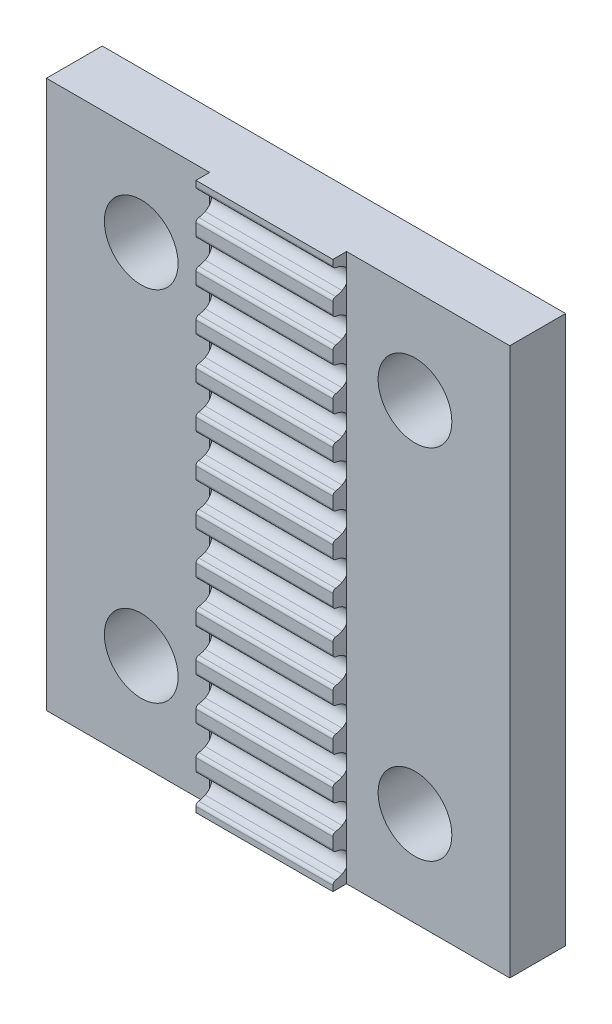
SolidWorks part; units mm, degrees
ref_plane "Piano frontale" through (0, 0, 0) normal (0, 0, 1) x (1, 0, 0)
ref_plane "Piano superiore" through (0, 0, 0) normal (0, 1, 0) x (1, 0, 0)
ref_plane "Piano destro" through (0, 0, 0) normal (1, 0, 0) x (0, 0, -1)
sketch "Schizzo1" plane through (0, 0, 0) normal (0, 0, 1) x (1, 0, 0)
  line L1 (-11, -13) -> (11, -13)
  line L2 (-11, -13) -> (-11, 13)
  line L3 (-11, 13) -> (11, 13)
  line L4 (11, -13) -> (11, 13)
  line L5 (-11, -13) -> (11, 13) construction
  line L6 (-11, 13) -> (11, -13) construction
  line L7 (-6.5, 8.5) -> (6.5, 8.5) construction
  line L8 (-6.5, 8.5) -> (-6.5, -8.5) construction
  line L9 (-6.5, -8.5) -> (6.5, -8.5) construction
  line L10 (6.5, 8.5) -> (6.5, -8.5) construction
  line L11 (-6.5, 8.5) -> (6.5, -8.5) construction
  line L12 (-6.5, -8.5) -> (6.5, 8.5) construction
  line L13 (-3.25, 13) -> (3.25, 13)
  line L14 (-3.25, 13) -> (-3.25, -13)
  line L15 (-3.25, -13) -> (3.25, -13)
  line L16 (3.25, 13) -> (3.25, -13)
  line L17 (-3.25, 13) -> (3.25, -13) construction
  line L18 (-3.25, -13) -> (3.25, 13) construction
  circle A0 centre (-6.5, 8.5) radius 1.75
  circle A1 centre (6.5, 8.5) radius 1.75
  circle A2 centre (6.5, -8.5) radius 1.75
  circle A3 centre (-6.5, -8.5) radius 1.75
  point P0 (0, 0)
  point P6 (0, 0)
  point P7 (0, 0)
  point P15 (0, 0)
  point P20 (0, 0)
  dimension "D3" = 3.5
  dimension "D1" = 22
  dimension "D2" = 26
  dimension "D5" = 6.5
  dimension "D6" = 4.5
  dimension "D7" = 4.5
extrude "Estrusione-Estrusione1" add sketch "Schizzo1" along normal blind 1 contours L14 L3 L2 L1 A3 A0 | L16 L3 L14 L1 | L3 L16 L1 L4 A2 A1 region at (-7.191, 0, 0) region at (0, 0, 0) region at (7.191, 0, 0)
extrude "Estrusione-Estrusione2" add sketch "Schizzo1<3>" along normal blind 1.65 contours L14 L15 L16 L13
sketch "Schizzo1<3>" plane through (0, 0, 0) normal (0, 0, 1) x (1, 0, 0) same geometry as "Schizzo1"
extrude "Estrusione-Estrusione3" add sketch "Schizzo1<5>" against normal blind 1.65 contours L14 L3 L2 L1 A3 A0 | L16 L3 L14 L1 | L3 L16 L1 L4 A2 A1 region at (-7.191, 0, 0) region at (0, 0, 0) region at (7.191, 0, 0)
sketch "Schizzo1<5>" plane through (0, 0, 0) normal (0, 0, 1) x (1, 0, 0) same geometry as "Schizzo1"
sketch "Schizzo2" plane through (-3.25, 0, 0) normal (-1, 0, 0) x (0, 0, 1)
  line L0 (1.65, 13) -> (1.65, 12.7402)
  line L2 (1.65, 13) -> (1, 13) construction
  line L3 (1.65, 13) -> (1, 13) construction
  line L4 (1.65, 11) -> (1.65, 10.7402)
  line L5 (2.28, 11) -> (2.28, 9)
  line L6 (1.65, 9) -> (1.65, 9.2598)
  line L7 (1.65, 13) -> (1.65, -13) construction
  line L8 (1.65, 13) -> (1.65, -13) construction
  line L9 (0.9, 12) -> (2.28, 12) construction
  line L10 (2.28, 13) -> (2.28, 11)
  line L11 (1.65, 11) -> (1.65, 11.2598)
  line L12 (1.65, 11) -> (1, 11) construction
  line L13 (0.9, 10) -> (2.28, 10) construction
  line L14 (1.65, 9) -> (1.65, 8.7402)
  line L15 (2.28, 9) -> (2.28, 7)
  line L16 (1.65, 7) -> (1.65, 7.2598)
  line L17 (1.65, 9) -> (1, 9) construction
  line L18 (0.9, 8) -> (2.28, 8) construction
  line L19 (1.65, 7) -> (1.65, 6.7402)
  line L20 (2.28, 7) -> (2.28, 5)
  line L21 (1.65, 5) -> (1.65, 5.2598)
  line L22 (1.65, 7) -> (1, 7) construction
  line L23 (0.9, 6) -> (2.28, 6) construction
  line L24 (1.65, 5) -> (1.65, 4.7402)
  line L25 (2.28, 5) -> (2.28, 3)
  line L26 (1.65, 3) -> (1.65, 3.2598)
  line L27 (1.65, 5) -> (1, 5) construction
  line L28 (0.9, 4) -> (2.28, 4) construction
  line L29 (1.65, 3) -> (1.65, 2.7402)
  line L30 (2.28, 3) -> (2.28, 1)
  line L31 (1.65, 1) -> (1.65, 1.2598)
  line L32 (1.65, 3) -> (1, 3) construction
  line L33 (0.9, 2) -> (2.28, 2) construction
  line L34 (1.65, 1) -> (1.65, 0.7402)
  line L35 (2.28, 1) -> (2.28, -1)
  line L36 (1.65, -1) -> (1.65, -0.7402)
  line L37 (1.65, 1) -> (1, 1) construction
  line L38 (0.9, 0) -> (2.28, 0) construction
  line L39 (1.65, -1) -> (1.65, -1.2598)
  line L40 (2.28, -1) -> (2.28, -3)
  line L41 (1.65, -3) -> (1.65, -2.7402)
  line L42 (1.65, -1) -> (1, -1) construction
  line L43 (0.9, -2) -> (2.28, -2) construction
  line L44 (1.65, -3) -> (1.65, -3.2598)
  line L45 (2.28, -3) -> (2.28, -5)
  line L46 (1.65, -5) -> (1.65, -4.7402)
  line L47 (1.65, -3) -> (1, -3) construction
  line L48 (0.9, -4) -> (2.28, -4) construction
  line L49 (1.65, -5) -> (1.65, -5.2598)
  line L50 (2.28, -5) -> (2.28, -7)
  line L51 (1.65, -7) -> (1.65, -6.7402)
  line L52 (1.65, -5) -> (1, -5) construction
  line L53 (0.9, -6) -> (2.28, -6) construction
  line L54 (1.65, -7) -> (1.65, -7.2598)
  line L55 (2.28, -7) -> (2.28, -9)
  line L56 (1.65, -9) -> (1.65, -8.7402)
  line L57 (1.65, -7) -> (1, -7) construction
  line L58 (0.9, -8) -> (2.28, -8) construction
  line L59 (1.65, -9) -> (1.65, -9.2598)
  line L60 (2.28, -9) -> (2.28, -11)
  line L61 (1.65, -11) -> (1.65, -10.7402)
  line L62 (1.65, -9) -> (1, -9) construction
  line L63 (0.9, -10) -> (2.28, -10) construction
  line L64 (1.65, -11) -> (1.65, -11.2598)
  line L65 (2.28, -11) -> (2.28, -13)
  line L66 (1.65, -13) -> (1.65, -12.7402)
  line L67 (1.65, -11) -> (1, -11) construction
  line L68 (0.9, -12) -> (2.28, -12) construction
  line L69 (1.65, -13) -> (2.28, -13)
  line L70 (2.28, 13) -> (1.65, 13)
  arc A0 (1.65, 12.7402) -> (1.5196, 12.5915) centre (1.5, 12.7402) cw
  arc A1 (1.2118, 12.4989) -> (1.5196, 12.5915) centre (1.65, 11.6) cw
  arc A2 (1.65, 10.7402) -> (1.5196, 10.5915) centre (1.5, 10.7402) cw
  arc A3 (1.2118, 10.4989) -> (1.5196, 10.5915) centre (1.65, 9.6) cw
  arc A4 (1.2118, 10.4989) -> (1.2118, 9.5011) centre (1.455, 10) ccw
  arc A5 (1.2118, 12.4989) -> (1.2118, 11.5011) centre (1.455, 12) ccw
  arc A6 (1.2118, 11.5011) -> (1.5196, 11.4085) centre (1.65, 12.4) ccw
  arc A7 (1.65, 11.2598) -> (1.5196, 11.4085) centre (1.5, 11.2598) ccw
  arc A8 (1.2118, 9.5011) -> (1.5196, 9.4085) centre (1.65, 10.4) ccw
  arc A9 (1.65, 9.2598) -> (1.5196, 9.4085) centre (1.5, 9.2598) ccw
  arc A10 (1.65, 8.7402) -> (1.5196, 8.5915) centre (1.5, 8.7402) cw
  arc A11 (1.2118, 8.4989) -> (1.5196, 8.5915) centre (1.65, 7.6) cw
  arc A12 (1.2118, 8.4989) -> (1.2118, 7.5011) centre (1.455, 8) ccw
  arc A13 (1.2118, 7.5011) -> (1.5196, 7.4085) centre (1.65, 8.4) ccw
  arc A14 (1.65, 7.2598) -> (1.5196, 7.4085) centre (1.5, 7.2598) ccw
  arc A15 (1.65, 6.7402) -> (1.5196, 6.5915) centre (1.5, 6.7402) cw
  arc A16 (1.2118, 6.4989) -> (1.5196, 6.5915) centre (1.65, 5.6) cw
  arc A17 (1.2118, 6.4989) -> (1.2118, 5.5011) centre (1.455, 6) ccw
  arc A18 (1.2118, 5.5011) -> (1.5196, 5.4085) centre (1.65, 6.4) ccw
  arc A19 (1.65, 5.2598) -> (1.5196, 5.4085) centre (1.5, 5.2598) ccw
  arc A20 (1.65, 4.7402) -> (1.5196, 4.5915) centre (1.5, 4.7402) cw
  arc A21 (1.2118, 4.4989) -> (1.5196, 4.5915) centre (1.65, 3.6) cw
  arc A22 (1.2118, 4.4989) -> (1.2118, 3.5011) centre (1.455, 4) ccw
  arc A23 (1.2118, 3.5011) -> (1.5196, 3.4085) centre (1.65, 4.4) ccw
  arc A24 (1.65, 3.2598) -> (1.5196, 3.4085) centre (1.5, 3.2598) ccw
  arc A25 (1.65, 2.7402) -> (1.5196, 2.5915) centre (1.5, 2.7402) cw
  arc A26 (1.2118, 2.4989) -> (1.5196, 2.5915) centre (1.65, 1.6) cw
  arc A27 (1.2118, 2.4989) -> (1.2118, 1.5011) centre (1.455, 2) ccw
  arc A28 (1.2118, 1.5011) -> (1.5196, 1.4085) centre (1.65, 2.4) ccw
  arc A29 (1.65, 1.2598) -> (1.5196, 1.4085) centre (1.5, 1.2598) ccw
  arc A30 (1.65, 0.7402) -> (1.5196, 0.5915) centre (1.5, 0.7402) cw
  arc A31 (1.2118, 0.4989) -> (1.5196, 0.5915) centre (1.65, -0.4) cw
  arc A32 (1.2118, 0.4989) -> (1.2118, -0.4989) centre (1.455, 0) ccw
  arc A33 (1.2118, -0.4989) -> (1.5196, -0.5915) centre (1.65, 0.4) ccw
  arc A34 (1.65, -0.7402) -> (1.5196, -0.5915) centre (1.5, -0.7402) ccw
  arc A35 (1.65, -1.2598) -> (1.5196, -1.4085) centre (1.5, -1.2598) cw
  arc A36 (1.2118, -1.5011) -> (1.5196, -1.4085) centre (1.65, -2.4) cw
  arc A37 (1.2118, -1.5011) -> (1.2118, -2.4989) centre (1.455, -2) ccw
  arc A38 (1.2118, -2.4989) -> (1.5196, -2.5915) centre (1.65, -1.6) ccw
  arc A39 (1.65, -2.7402) -> (1.5196, -2.5915) centre (1.5, -2.7402) ccw
  arc A40 (1.65, -3.2598) -> (1.5196, -3.4085) centre (1.5, -3.2598) cw
  arc A41 (1.2118, -3.5011) -> (1.5196, -3.4085) centre (1.65, -4.4) cw
  arc A42 (1.2118, -3.5011) -> (1.2118, -4.4989) centre (1.455, -4) ccw
  arc A43 (1.2118, -4.4989) -> (1.5196, -4.5915) centre (1.65, -3.6) ccw
  arc A44 (1.65, -4.7402) -> (1.5196, -4.5915) centre (1.5, -4.7402) ccw
  arc A45 (1.65, -5.2598) -> (1.5196, -5.4085) centre (1.5, -5.2598) cw
  arc A46 (1.2118, -5.5011) -> (1.5196, -5.4085) centre (1.65, -6.4) cw
  arc A47 (1.2118, -5.5011) -> (1.2118, -6.4989) centre (1.455, -6) ccw
  arc A48 (1.2118, -6.4989) -> (1.5196, -6.5915) centre (1.65, -5.6) ccw
  arc A49 (1.65, -6.7402) -> (1.5196, -6.5915) centre (1.5, -6.7402) ccw
  arc A50 (1.65, -7.2598) -> (1.5196, -7.4085) centre (1.5, -7.2598) cw
  arc A51 (1.2118, -7.5011) -> (1.5196, -7.4085) centre (1.65, -8.4) cw
  arc A52 (1.2118, -7.5011) -> (1.2118, -8.4989) centre (1.455, -8) ccw
  arc A53 (1.2118, -8.4989) -> (1.5196, -8.5915) centre (1.65, -7.6) ccw
  arc A54 (1.65, -8.7402) -> (1.5196, -8.5915) centre (1.5, -8.7402) ccw
  arc A55 (1.65, -9.2598) -> (1.5196, -9.4085) centre (1.5, -9.2598) cw
  arc A56 (1.2118, -9.5011) -> (1.5196, -9.4085) centre (1.65, -10.4) cw
  arc A57 (1.2118, -9.5011) -> (1.2118, -10.4989) centre (1.455, -10) ccw
  arc A58 (1.2118, -10.4989) -> (1.5196, -10.5915) centre (1.65, -9.6) ccw
  arc A59 (1.65, -10.7402) -> (1.5196, -10.5915) centre (1.5, -10.7402) ccw
  arc A60 (1.65, -11.2598) -> (1.5196, -11.4085) centre (1.5, -11.2598) cw
  arc A61 (1.2118, -11.5011) -> (1.5196, -11.4085) centre (1.65, -12.4) cw
  arc A62 (1.2118, -11.5011) -> (1.2118, -12.4989) centre (1.455, -12) ccw
  arc A63 (1.2118, -12.4989) -> (1.5196, -12.5915) centre (1.65, -11.6) ccw
  arc A64 (1.65, -12.7402) -> (1.5196, -12.5915) centre (1.5, -12.7402) ccw
  point P26 (1.65, 12.4)
  point P37 (1.65, 10.4)
  point P57 (1.65, 8.4)
  point P77 (1.65, 6.4)
  point P97 (1.65, 4.4)
  point P117 (1.65, 2.4)
  point P137 (1.65, 0.4)
  point P157 (1.65, -1.6)
  point P177 (1.65, -3.6)
  point P197 (1.65, -5.6)
  point P217 (1.65, -7.6)
  point P237 (1.65, -9.6)
  point P257 (1.65, -11.6)
  dimension "D2" = 1
  dimension "D3" = 0.15
  dimension "D4" = 0.75
  dimension "D5" = 1.38
  dimension "D6" = 1
  dimension "D7" = 13
  dimension "D8" = 0.63
  dimension "D9" = 0.4
extrude "Taglio-Estrusione1" cut sketch "Schizzo2" against normal up to surface (6.5 mm away) up to face at (3.25, 0, 1.325)
